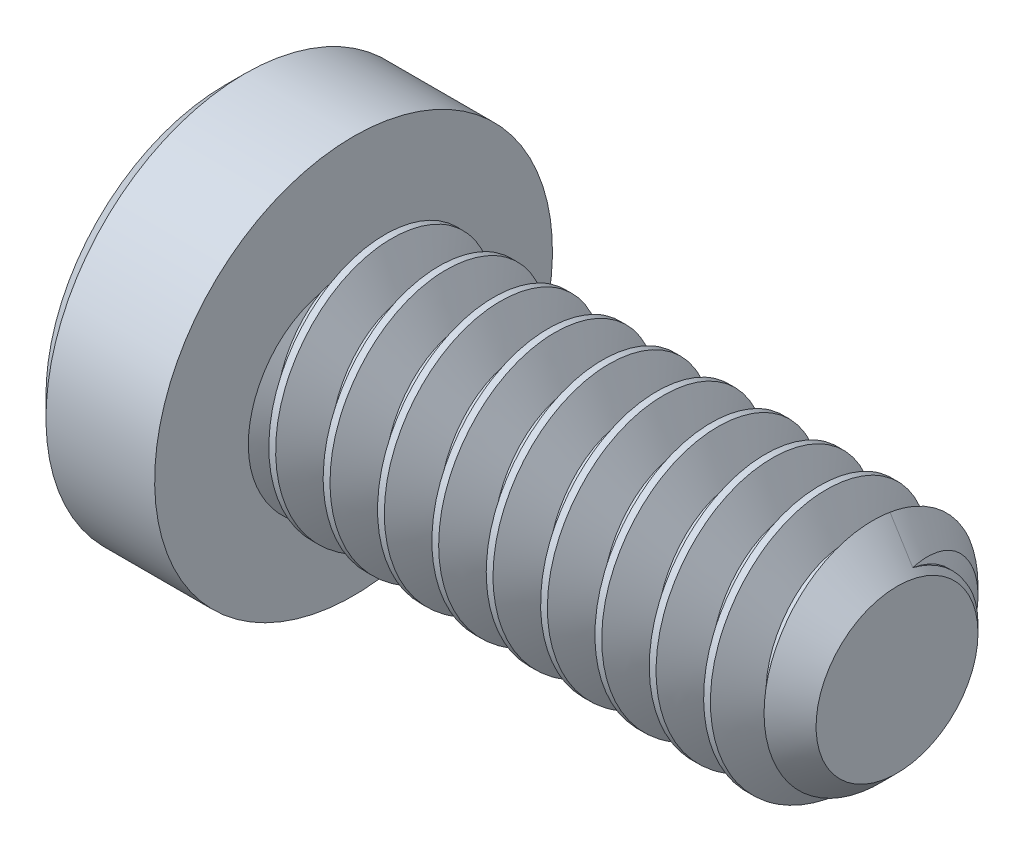
SolidWorks part; units mm, degrees
ref_plane "Front Plane" through (0, 0, 0) normal (0, 0, 1) x (1, 0, 0)
ref_plane "Top Plane" through (0, 0, 0) normal (0, 1, 0) x (1, 0, 0)
ref_plane "Right Plane" through (0, 0, 0) normal (1, 0, 0) x (0, 0, -1)
sketch "Sketch1" plane through (0, 0, 0) normal (0, 0, 1) x (1, 0, 0)
  line L0 (3.175, 0) -> (-3.175, 0) construction
  line L1 (3.175, 1.4224) -> (3.175, -1.4224) construction
  line L2 (-3.175, 2.3241) -> (-3.175, -2.3241) construction
  line L3 (-3.175, 2.3241) -> (-4.445, 2.3241) construction
  line L4 (-4.445, 2.3241) -> (-4.6736, 2.0955) construction
  line L5 (-4.6736, 2.0955) -> (-4.6736, -2.0955) construction
  line L6 (-4.6736, -2.0955) -> (-4.445, -2.3241) construction
  line L7 (-4.445, -2.3241) -> (-3.175, -2.3241) construction
  point P7 (-3.7084, 0)
  point P12 (0.635, -1.4224)
  dimension "D1" = 45
  dimension "D2" = 2.54
  dimension "Dec." = 2.8448
  dimension "Length" = 6.35
  dimension "Head Dia" = 4.6482
  dimension "Head Height" = 1.4986
  dimension "Hex Depth" = 0.9652
  dimension "Chamfer" = 0.2286
ref_plane "Plane1" through (3.175, 0, 0) normal (1, 0, 0) x (0, 0, -1)
ref_plane "Plane2" through (-4.6736, 0, 0) normal (1, 0, 0) x (0, 0, -1)
sketch "Sketch2" plane through (3.175, 0, 0) normal (1, 0, 0) x (0, 0, -1)
  circle A0 centre (0, 0) radius 1.4224
extrude "Boss-Extrude1" add sketch "Sketch2" against normal up to vertex (6.35 mm away) up to point (-3.175, 0, 0)
sketch "Sketch3" plane through (3.175, 0, 0) normal (1, 0, 0) x (0, 0, -1)
  circle A0 centre (0, 0) radius 1.4224 construction
  circle A1 centre (0, 0) radius 1.4224
curve "Helix/Spiral1" pitch 0.635 height 6.985 radius 1.4224 centre (3.175, 0, 0) axis (-1, 0, 0) start towards (0, 1, 0) parameters "Pitch"=0.635
chamfer "Chamfer1" distance 0.4763 angle 45 1 edges at (3.175, 0, -1.4224)
sketch "Sketch5" plane through (0, 0, 0) normal (0, 0, 1) x (1, 0, 0)
  line L0 (2.8972, 1.4224) -> (3.4528, 1.4224)
  line L1 (3.4528, 1.4224) -> (3.2147, 1.01)
  line L2 (3.2147, 1.01) -> (3.1353, 1.01)
  line L3 (3.1353, 1.01) -> (2.8972, 1.4224)
  line L4 (3.175, 1.01) -> (3.175, 1.4224) construction
  line L5 (3.0162, 1.2162) -> (3.3337, 1.2162) construction
  dimension "D1" = 60
  dimension "D2" = 0.3175
  dimension "D3" = 0.0794
sweep "Cut-Sweep1" cut profiles "Sketch5" path "Helix/Spiral1"
sketch "Sketch4" plane through (-4.6736, 0, 0) normal (1, 0, 0) x (0, 0, -1)
  line L0 (-2.3241, 0.7937) -> (2.3241, 0.7937) construction
  line L1 (0, 0.7332) -> (-0.635, 0.3666)
  line L2 (-0.635, 0.3666) -> (-0.635, -0.3666)
  line L3 (-0.635, -0.3666) -> (0, -0.7332)
  line L4 (0, -0.7332) -> (0.635, -0.3666)
  line L5 (0.635, -0.3666) -> (0.635, 0.3666)
  line L6 (0.635, 0.3666) -> (0, 0.7332)
  line L7 (0, 0) -> (0, 0.7937) construction
  circle A0 centre (0, 0) radius 0.635 construction
  dimension "D1" = 4.6482
  dimension "Hex Size" = 1.27
  dimension "D2" = 0.7937
sketch "Sketch6" plane through (0, 0, 0) normal (0, 0, 1) x (1, 0, 0)
  line L0 (-4.445, 2.3241) -> (-4.6736, 2.0955) construction
  line L1 (-3.175, 2.3241) -> (-4.445, 2.3241) construction
  line L2 (-3.175, 2.3241) -> (-3.175, -2.3241) construction
  line L3 (-4.6736, 2.0955) -> (-4.6736, -2.0955) construction
  line L4 (-4.445, 2.3241) -> (-4.6736, 2.0955)
  line L5 (-3.175, 2.3241) -> (-4.445, 2.3241)
  line L6 (-3.175, 2.3241) -> (-3.175, 0)
  line L7 (-4.6736, 2.0955) -> (-4.6736, 0)
  line L8 (-3.175, 0) -> (-4.6736, 0) construction
  line L9 (-3.175, 0) -> (-4.6736, 0)
revolve "Revolve1" add sketch "Sketch6" angle 360 about L8
extrude "Cut-Extrude1" cut sketch "Sketch4" along normal up to vertex (0.9652 mm away) up to point (-3.7084, 0, 0)
sketch "Sketch8" plane through (-4.6736, 0, 0) normal (-1, 0, 0) x (0, 0, 1)
  circle A1 centre (0, 0) radius 0.7332
extrude "Cut-Extrude2" cut sketch "Sketch8" against normal through all draft 45
equation "\"D3@Helix/Spiral1\" = \"Length@Sketch1\"+\"Pitch@Helix/Spiral1\""
equation "\"D3@Sketch5\" = \"Pitch@Helix/Spiral1\"*.125"
equation "\"D2@Sketch5\" = \"Pitch@Helix/Spiral1\"*.50"
equation "\"D1@Chamfer1\" = \"Pitch@Helix/Spiral1\"*.75"
equation "\"D2@Sketch1\" = \"Pitch@Helix/Spiral1\"*4"
equation "\"D1@Sketch4\" = \"Head Dia@Sketch1\""
